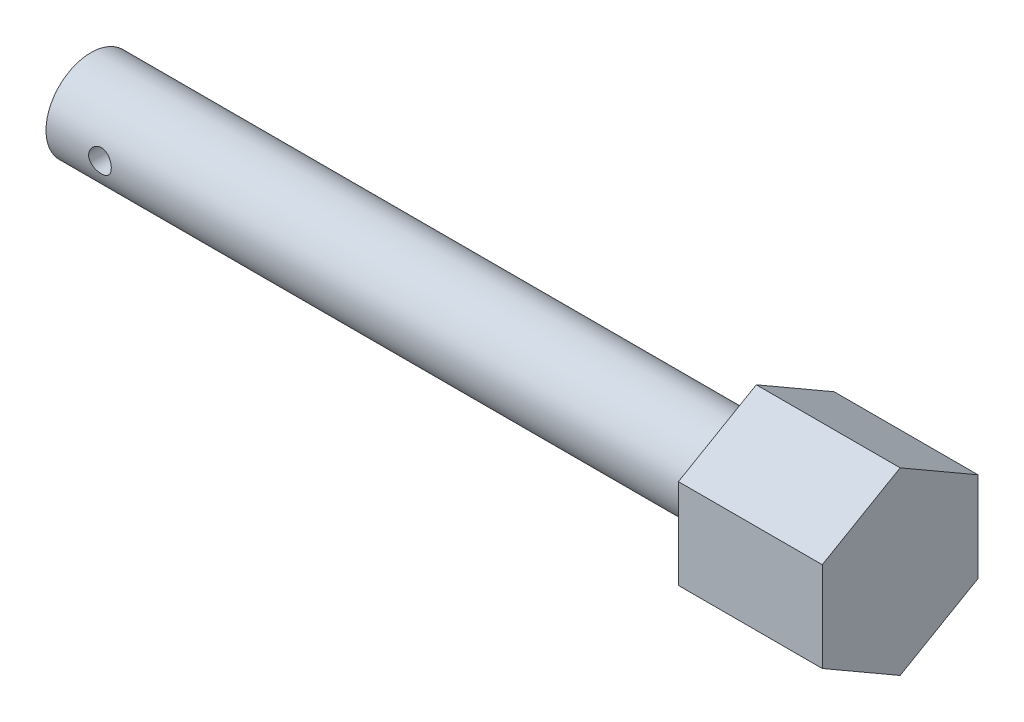
SolidWorks part; units mm, degrees
ref_plane "Front Plane" through (0, 0, 0) normal (0, 0, 1) x (1, 0, 0)
ref_plane "Top Plane" through (0, 0, 0) normal (0, 1, 0) x (1, 0, 0)
ref_plane "Right Plane" through (0, 0, 0) normal (1, 0, 0) x (0, 0, -1)
sketch "Sketch1" plane through (0, 0, 0) normal (1, 0, 0) x (0, 0, -1)
  circle A0 centre (0, 0) radius 3.175
extrude "Boss-Extrude2" add sketch "Sketch1" along normal blind 46.99 contours A0
sketch "Sketch2" plane through (46.99, 0, 0) normal (1, 0, 0) x (0, 0, -1)
  line L1 (-5.4993, 3.175) -> (-5.4993, -3.175)
  line L2 (-5.4993, -3.175) -> (0, -6.35)
  line L3 (0, -6.35) -> (5.4993, -3.175)
  line L4 (5.4993, -3.175) -> (5.4993, 3.175)
  line L5 (5.4993, 3.175) -> (0, 6.35)
  line L6 (0, 6.35) -> (-5.4993, 3.175)
  circle A0 centre (0, 0) radius 5.4993 construction
  dimension "D1" = 6.35
extrude "Boss-Extrude3" add sketch "Sketch2" along normal blind 10.16
sketch "Sketch3" plane through (0, 0, 0) normal (-1, 0, 0) x (0, 0, 1)
  circle A0 centre (0, 0) radius 1.778
  circle A1 centre (0, 0) radius 3.175
extrude "Cut-Extrude1" cut sketch "Sketch3" against normal blind 19.05
sketch "Sketch6" plane through (0, 0, 0) normal (-1, 0, 0) x (0, 0, 1)
  circle A0 centre (0, 0) radius 3.175
extrude "Boss-Extrude5" add sketch "Sketch6" against normal blind 49.022
sketch "Sketch7" plane through (0, 0, 0) normal (-1, 0, 0) x (0, 0, 1)
  line L1 (-0.4893, 0.7146) -> (-0.8635, -0.0664)
  line L2 (-0.8635, -0.0664) -> (-0.3742, -0.781)
  line L3 (-0.3742, -0.781) -> (0.4893, -0.7146)
  line L4 (0.4893, -0.7146) -> (0.8635, 0.0664)
  line L5 (0.8635, 0.0664) -> (0.3742, 0.781)
  line L6 (0.3742, 0.781) -> (-0.4893, 0.7146)
  circle A0 centre (0, 0) radius 0.75 construction
extrude "Cut-Extrude5" cut sketch "Sketch7" against normal blind 38.1
sketch "Sketch9" plane through (0, 0, 0) normal (-1, 0, 0) x (0, 0, 1)
  circle A0 centre (0, 0) radius 0.866
extrude "Cut-Extrude7" cut sketch "Sketch9" against normal blind 46.99 contours A0
sketch "Sketch10" plane through (0, 0, 5.4993) normal (0, 0, 1) x (1, 0, 0)
  line L0 (0, -3.175) -> (46.99, -3.175) construction
  circle A0 centre (3.81, 0) radius 0.8001
  dimension "D1" = 1.6002
  dimension "D2" = 3.81
  dimension "D3" = 3.175
extrude "Cut-Extrude8" cut sketch "Sketch10" against normal blind 5.334 contours A0
